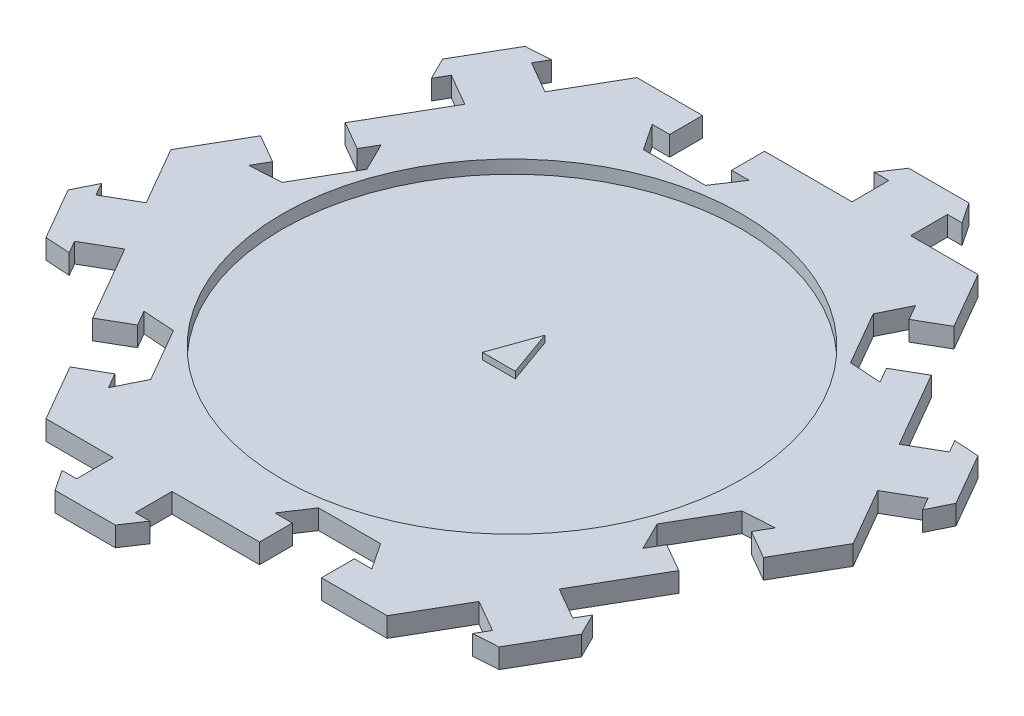
SolidWorks part; units mm, degrees
ref_plane "Front Plane" through (0, 0, 0) normal (0, 0, 1) x (1, 0, 0)
ref_plane "Top Plane" through (0, 0, 0) normal (0, 1, 0) x (1, 0, 0)
ref_plane "Right Plane" through (0, 0, 0) normal (1, 0, 0) x (0, 0, -1)
sketch "Sketch1" plane through (0, 0, 0) normal (0, 1, 0) x (1, 0, 0)
  line L0 (-15.9808, 45) -> (-15.9808, 40)
  line L1 (25.9808, -45) -> (51.9615, 0)
  line L2 (51.9615, 0) -> (25.9808, 45)
  line L3 (25.9808, 45) -> (-25.9808, 45)
  line L4 (-25.9808, 45) -> (-51.9615, 0)
  line L5 (-51.9615, 0) -> (-25.9808, -45)
  line L6 (-25.9808, -45) -> (25.9808, -45)
  line L7 (-15.9808, 40) -> (-18.6446, 40)
  line L8 (-18.6446, 40) -> (-15.9808, 36)
  line L9 (-15.9808, 36) -> (-6.5403, 36)
  line L10 (-6.5403, 36) -> (-3.8765, 40)
  line L11 (-3.8765, 40) -> (-6.5403, 40)
  line L12 (-6.5403, 40) -> (-6.5403, 45)
  line L13 (-15.9808, 40) -> (-15.9808, 36) construction
  line L14 (6.5403, 45) -> (6.5403, 50) construction
  line L15 (6.5403, 50) -> (3.8765, 50) construction
  line L16 (3.8765, 50) -> (6.5403, 54) construction
  line L17 (6.5403, 54) -> (15.9808, 54) construction
  line L18 (15.9808, 54) -> (18.6446, 50) construction
  line L19 (18.6446, 50) -> (15.9808, 50) construction
  line L20 (15.9808, 50) -> (15.9808, 45) construction
  line L21 (6.5403, 50) -> (6.5403, 54) construction
  line L22 (6.7903, 50.25) -> (6.7903, 45)
  line L23 (6.7903, 50.25) -> (4.3433, 50.25) construction
  line L24 (4.3433, 50.25) -> (6.6742, 53.75) construction
  line L25 (6.6742, 53.75) -> (15.8469, 53.75) construction
  line L26 (15.8469, 53.75) -> (18.1777, 50.25) construction
  line L27 (18.1777, 50.25) -> (15.7308, 50.25) construction
  line L28 (15.7308, 50.25) -> (15.7308, 45)
  line L29 (15.7308, 50.25) -> (15.7308, 50.6)
  line L30 (7.0097, 50.6) -> (4.5764, 50.6)
  line L31 (4.5764, 50.6) -> (6.6742, 53.75)
  line L32 (6.6742, 53.75) -> (15.8469, 53.75)
  line L33 (15.8469, 53.75) -> (17.9446, 50.6)
  line L34 (17.9446, 50.6) -> (15.5089, 50.6)
  line L35 (6.7903, 50.25) -> (6.7903, 50.6)
  line L36 (30.9808, 36.3397) -> (26.6506, 33.8397)
  line L37 (26.6506, 33.8397) -> (25.3187, 36.1467)
  line L38 (25.3187, 36.1467) -> (23.1865, 31.8397)
  line L39 (23.1865, 31.8397) -> (27.9068, 23.664)
  line L40 (27.9068, 23.664) -> (32.7028, 23.3571)
  line L41 (32.7028, 23.3571) -> (31.3709, 25.664)
  line L42 (31.3709, 25.664) -> (35.701, 28.164)
  line L43 (51.3832, 11.5018) -> (46.8365, 8.8768)
  line L44 (46.9129, 19.2444) -> (42.3663, 16.6194)
  line L45 (46.9129, 19.2444) -> (47.216, 19.4194)
  line L46 (51.3832, 11.5018) -> (51.6863, 11.6768)
  line L47 (52.7932, 9.7595) -> (51.5754, 11.8689)
  line L48 (54.4723, 13.1512) -> (52.7932, 9.7595)
  line L49 (49.8859, 21.095) -> (54.4723, 13.1512)
  line L50 (46.1091, 21.3367) -> (49.8859, 21.095)
  line L51 (47.3257, 19.2294) -> (46.1091, 21.3367)
  line L52 (46.9615, -8.6603) -> (42.6314, -6.1603)
  line L53 (42.6314, -6.1603) -> (43.9633, -3.8533)
  line L54 (43.9633, -3.8533) -> (39.1673, -4.1603)
  line L55 (39.1673, -4.1603) -> (34.4471, -12.336)
  line L56 (34.4471, -12.336) -> (36.5793, -16.6429)
  line L57 (36.5793, -16.6429) -> (37.9112, -14.336)
  line L58 (37.9112, -14.336) -> (42.2413, -16.836)
  line L59 (35.6524, -38.7482) -> (31.1058, -36.1232)
  line L60 (40.1226, -31.0056) -> (35.576, -28.3806)
  line L61 (40.1226, -31.0056) -> (40.4257, -31.1806)
  line L62 (35.6524, -38.7482) -> (35.9555, -38.9232)
  line L63 (34.8486, -40.8405) -> (36.0664, -38.7311)
  line L64 (38.6254, -40.5988) -> (34.8486, -40.8405)
  line L65 (43.2118, -32.655) -> (38.6254, -40.5988)
  line L66 (41.5327, -29.2633) -> (43.2118, -32.655)
  line L67 (40.316, -31.3706) -> (41.5327, -29.2633)
  line L68 (15.9808, -45) -> (15.9808, -40)
  line L69 (15.9808, -40) -> (18.6446, -40)
  line L70 (18.6446, -40) -> (15.9808, -36)
  line L71 (15.9808, -36) -> (6.5403, -36)
  line L72 (6.5403, -36) -> (3.8765, -40)
  line L73 (3.8765, -40) -> (6.5403, -40)
  line L74 (6.5403, -40) -> (6.5403, -45)
  line L75 (-15.7308, -50.25) -> (-15.7308, -45)
  line L76 (-6.7903, -50.25) -> (-6.7903, -45)
  line L77 (-6.7903, -50.25) -> (-6.7903, -50.6)
  line L78 (-15.7308, -50.25) -> (-15.7308, -50.6)
  line L79 (-17.9446, -50.6) -> (-15.5089, -50.6)
  line L80 (-15.8469, -53.75) -> (-17.9446, -50.6)
  line L81 (-6.6742, -53.75) -> (-15.8469, -53.75)
  line L82 (-4.5764, -50.6) -> (-6.6742, -53.75)
  line L83 (-7.0097, -50.6) -> (-4.5764, -50.6)
  line L84 (-30.9808, -36.3397) -> (-26.6506, -33.8397)
  line L85 (-26.6506, -33.8397) -> (-25.3187, -36.1467)
  line L86 (-25.3187, -36.1467) -> (-23.1865, -31.8397)
  line L87 (-23.1865, -31.8397) -> (-27.9068, -23.664)
  line L88 (-27.9068, -23.664) -> (-32.7028, -23.3571)
  line L89 (-32.7028, -23.3571) -> (-31.3709, -25.664)
  line L90 (-31.3709, -25.664) -> (-35.701, -28.164)
  line L91 (-51.3832, -11.5018) -> (-46.8365, -8.8768)
  line L92 (-46.9129, -19.2444) -> (-42.3663, -16.6194)
  line L93 (-46.9129, -19.2444) -> (-47.216, -19.4194)
  line L94 (-51.3832, -11.5018) -> (-51.6863, -11.6768)
  line L95 (-52.7932, -9.7595) -> (-51.5754, -11.8689)
  line L96 (-54.4723, -13.1512) -> (-52.7932, -9.7595)
  line L97 (-49.8859, -21.095) -> (-54.4723, -13.1512)
  line L98 (-46.1091, -21.3367) -> (-49.8859, -21.095)
  line L99 (-47.3257, -19.2294) -> (-46.1091, -21.3367)
  line L100 (-46.9615, 8.6603) -> (-42.6314, 6.1603)
  line L101 (-42.6314, 6.1603) -> (-43.9633, 3.8533)
  line L102 (-43.9633, 3.8533) -> (-39.1673, 4.1603)
  line L103 (-39.1673, 4.1603) -> (-34.4471, 12.336)
  line L104 (-34.4471, 12.336) -> (-36.5793, 16.6429)
  line L105 (-36.5793, 16.6429) -> (-37.9112, 14.336)
  line L106 (-37.9112, 14.336) -> (-42.2413, 16.836)
  line L107 (-35.6524, 38.7482) -> (-31.1058, 36.1232)
  line L108 (-40.1226, 31.0056) -> (-35.576, 28.3806)
  line L109 (-40.1226, 31.0056) -> (-40.4257, 31.1806)
  line L110 (-35.6524, 38.7482) -> (-35.9555, 38.9232)
  line L111 (-34.8486, 40.8405) -> (-36.0664, 38.7311)
  line L112 (-38.6254, 40.5988) -> (-34.8486, 40.8405)
  line L113 (-43.2118, 32.655) -> (-38.6254, 40.5988)
  line L114 (-41.5327, 29.2633) -> (-43.2118, 32.655)
  line L115 (-40.316, 31.3706) -> (-41.5327, 29.2633)
  line L116 (6.7903, 45) -> (6.7903, 50.25) construction
  line L117 (15.7308, 50.25) -> (15.7308, 45) construction
  line L118 (0, 5) -> (0, -2) construction
  line L119 (2.5, -2) -> (0, 5)
  line L120 (0, 5) -> (-2.5, -2)
  line L121 (-2.5, -2) -> (2.5, -2)
  circle A0 centre (0, 0) radius 45 construction
  circle A1 centre (0, 0) radius 45 construction
  circle A2 centre (0, 0) radius 35
  point P145 (0, 0)
  point P146 (-0.0013, -0.0009)
  dimension "D1" = 90
  dimension "D4" = 10
  dimension "D2" = 5
  dimension "D3" = 4
  dimension "D5" = 10
  dimension "D6" = 0.25
  dimension "D7" = 0.35
  dimension "D8" = 6
  dimension "D10" = 0.6
  dimension "D9" = 0.25
  dimension "D12" = 5
  dimension "D13" = 7
  dimension "D14" = 2
  dimension "D11" = 10
extrude "Boss-Extrude1" add sketch "Sketch1" along normal blind 3 contours L2 L3 L4 | L3 | L2 | L4 | L1 | L5 | L6 region at (-17.3555, 0, -42.5) region at (11.2605, 0, -49.5746) region at (-37.3026, 0, -34.5392) region at (48.5631, 0, -15.0354) region at (-48.5631, 0, 15.0354) region at (37.3026, 0, 34.5392) region at (-11.2605, 0, 49.5746)
extrude "Boss-Extrude2" add sketch "Sketch1<3>" along normal blind 1 contours A2 region at (-34.0101, 0, 0)
sketch "Sketch1<3>" plane through (0, 0, 0) normal (0, 1, 0) x (1, 0, 0) same geometry as "Sketch1"
extrude "Boss-Extrude3" add sketch "Sketch1<4>" along normal blind 2 contours L120 L121 L119 region at (0, 0, -0.3333)
sketch "Sketch1<4>" plane through (0, 0, 0) normal (0, 1, 0) x (1, 0, 0) same geometry as "Sketch1"
